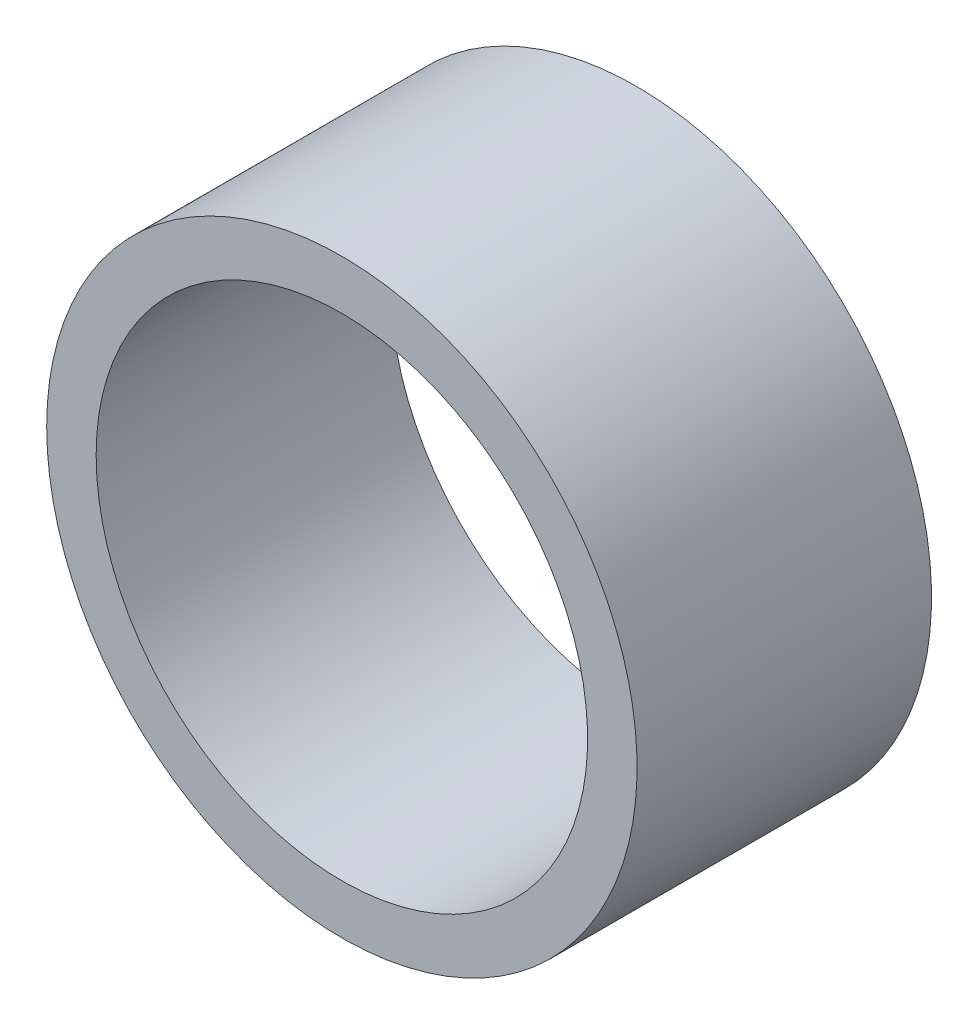
SolidWorks part; units mm, degrees
ref_plane "Front Plane" through (0, 0, 0) normal (0, 0, 1) x (1, 0, 0)
ref_plane "Top Plane" through (0, 0, 0) normal (0, 1, 0) x (1, 0, 0)
ref_plane "Right Plane" through (0, 0, 0) normal (1, 0, 0) x (0, 0, -1)
sketch "Sketch1" plane through (0, 0, 0) normal (0, 0, 1) x (1, 0, 0)
  circle A0 centre (0, 0) radius 9.5504
  circle A1 centre (0, 0) radius 7.9502
  dimension "OD" = 19.1008
  dimension "ID" = 15.9004
sketch "Sketch2" plane through (0, 0, 0) normal (1, 0, 0) x (0, 0, -1)
  line L2 (4.7625, 0) -> (-4.7625, 0) construction
  line L4 (-4.7625, -9.5504) -> (-4.7625, 9.5504) construction
  line L5 (-4.7625, -7.9502) -> (4.7625, -7.9502)
  line L6 (4.7625, 7.9502) -> (-4.7625, 7.9502)
  line L7 (4.7625, -9.5504) -> (4.7625, 9.5504) construction
  line L8 (-4.7625, 9.5504) -> (4.7625, 9.5504) construction
  line L9 (-4.7625, -9.5504) -> (4.7625, -9.5504) construction
  line L10 (0, 9.5504) -> (0, -9.5504) construction
  line L11 (0, 7.9502) -> (0, -7.9502) construction
  point P4 (0, -7.9502)
  point P7 (0, 7.9502)
  point P8 (0, 0)
  point P12 (-4.7625, 0)
  point P15 (4.7625, 0)
  point P16 (0, -9.5504)
  point P17 (0, 9.5504)
  dimension "Length" = 9.525
sketch "Sketch5" plane through (0, 0, 0) normal (0, 0, 1) x (1, 0, 0)
  circle A1 centre (0, 0) radius 7.9502
  circle A2 centre (0, 0) radius 7.9502
  circle A3 centre (0, 0) radius 9.5504
  circle A4 centre (0, 0) radius 9.5504
  dimension "D1" = 0
  dimension "D2" = 0
extrude "Boss-Extrude1" add sketch "Sketch5" along normal up to vertex and the other way up to vertex up to point (0, 0, 4.7625) other way up to point (0, 0, -4.7625)
sketch "Sketch4" plane through (0, 0, 4.7625) normal (0, 0, 1) x (1, 0, 0)
  line L0 (0, 0) -> (-5.6216, 5.6216)
  line L2 (0, -9.5504) -> (0, 9.5504) construction
  circle A1 centre (0, 0) radius 7.9502 construction
  dimension "D1" = 45
equation "\"D1\"= \"Length@Sketch2\""
